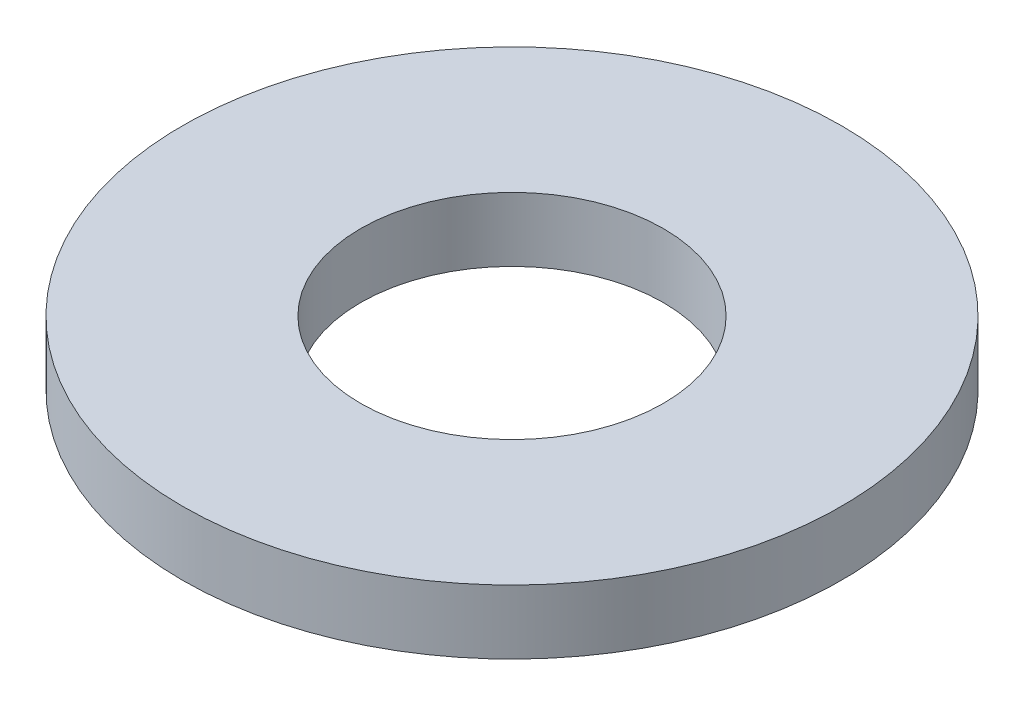
SolidWorks part; units mm, degrees
ref_plane "Front Plane" through (0, 0, 0) normal (0, 0, 1) x (1, 0, 0)
ref_plane "Top Plane" through (0, 0, 0) normal (0, 1, 0) x (1, 0, 0)
ref_plane "Right Plane" through (0, 0, 0) normal (1, 0, 0) x (0, 0, -1)
sketch "Sketch1" plane through (0, 0, 0) normal (0, 1, 0) x (1, 0, 0)
  circle A0 centre (0, 0) radius 92.5
  dimension "FLANGE_OD" = 185
extrude "Boss-Extrude1" add sketch "Sketch1" along normal blind 18
sketch "Sketch2" plane through (0, 0, 0) normal (0, 1, 0) x (1, 0, 0)
  circle A0 centre (0, 0) radius 42.5
  dimension "BORE_D" = 85
extrude "Cut-Extrude1" cut sketch "Sketch2" along normal through all
sketch "Sketch3" plane through (0, 18, 0) normal (0, 1, 0) x (1, 0, 0)
  circle A0 centre (0, 0) radius 24.5296 construction
  circle A1 centre (-24.5296, 0) radius 2.8779
  dimension "BOLT_D" = 5.7558
  dimension "BOLT_PCD" = 49.0591
extrude "Cut-Extrude2" cut sketch "Sketch3" against normal blind 14.8887 rebuild error yes
pattern_circular "CirPattern1" count 4 over 360 rebuild error yes
